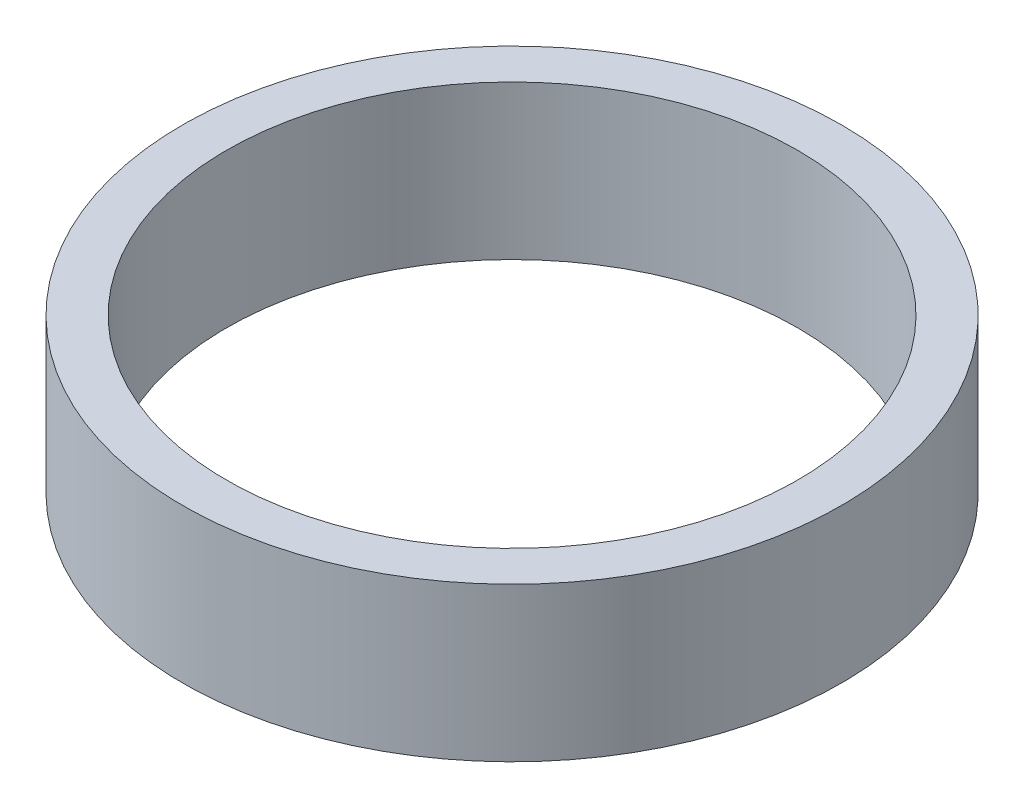
SolidWorks part; units mm, degrees
ref_plane "Plan1" through (0, 0, 0) normal (0, 0, 1) x (1, 0, 0)
ref_plane "Plan2" through (0, 0, 0) normal (0, 1, 0) x (1, 0, 0)
ref_plane "Plan3" through (0, 0, 0) normal (1, 0, 0) x (0, 0, -1)
ref_axis "Axe" through (0, 15.2289, 0) along (0, -1, 0)
sketch "Esquisse1" plane through (0, 0, 0) normal (0, 0, 1) x (1, 0, 0)
  line L1 (0, 0) -> (0, 2.5443) construction
  line L2 (6.5, 0) -> (6.5, 3.5)
  line L3 (6.5, 0) -> (7.5, 0)
  line L4 (7.5, 0) -> (7.5, 3.5)
  line L5 (7.5, 3.5) -> (6.5, 3.5)
  line L6 (6.5, 0) -> (-6.5, 0) construction
  line L7 (7.5, 0) -> (-7.5, 0) construction
  dimension "Epaisseur" = 3.5
  dimension "Rint" = 6.5
  dimension "Rext" = 7.5
  dimension "Diamètre de passage" = 13
  dimension "Diamètre extérieur" = 15
revolve "Base" add sketch "Esquisse1" angle 360 about L1
equation "\"Rext@Esquisse1\"=\"Diamètre extérieur@Esquisse1\"/2"
equation "\"Rint@Esquisse1\" = \"Diamètre de passage@Esquisse1\"/2"
